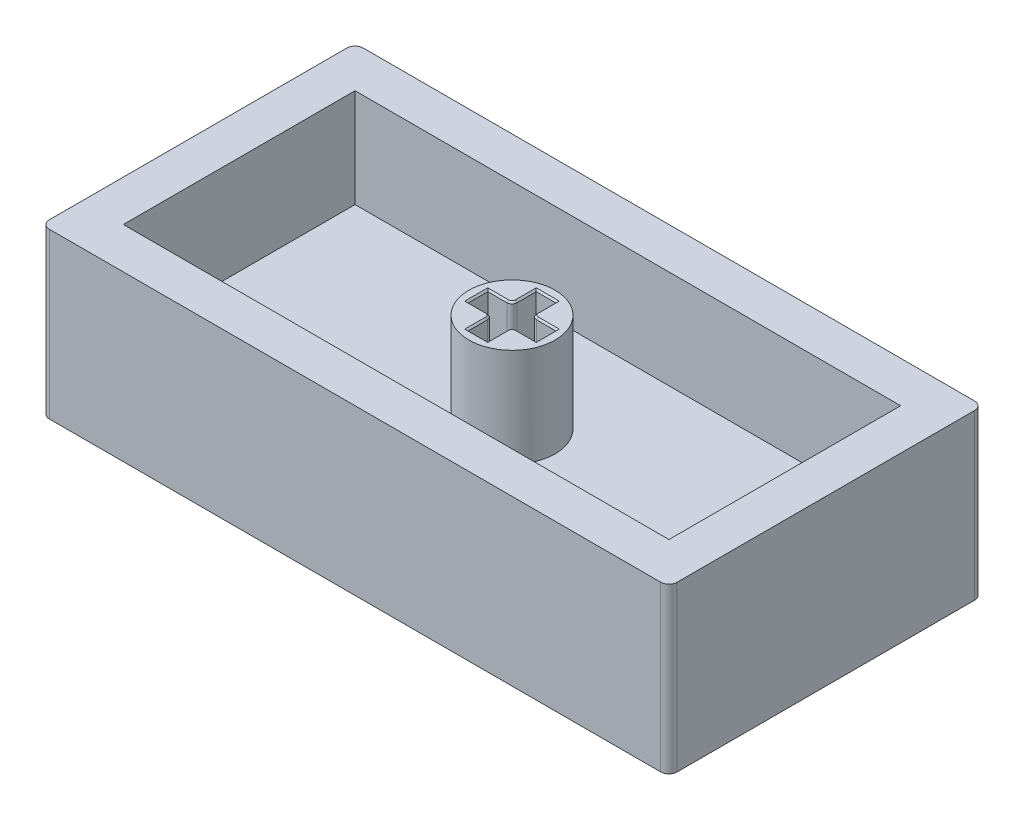
SolidWorks part; units mm, degrees
ref_plane "Front Plane" through (0, 0, 0) normal (0, 0, 1) x (1, 0, 0)
ref_plane "Top Plane" through (0, 0, 0) normal (0, 1, 0) x (1, 0, 0)
ref_plane "Right Plane" through (0, 0, 0) normal (1, 0, 0) x (0, 0, -1)
sketch "Sketch1" plane through (0, 0, 0) normal (0, 1, 0) x (1, 0, 0)
  line L0 (-16.6, -7.05) -> (-16.6, 7.05)
  line L1 (-7.05, -7.05) -> (7.05, -7.05) construction
  line L2 (-7.05, -7.05) -> (-7.05, 7.05) construction
  line L3 (-7.05, 7.05) -> (7.05, 7.05) construction
  line L4 (7.05, -7.05) -> (7.05, 7.05) construction
  line L5 (-7.05, -7.05) -> (7.05, 7.05) construction
  line L6 (-7.05, 7.05) -> (7.05, -7.05) construction
  line L7 (-19.1, -9.55) -> (19.1, -9.55)
  line L8 (-19.1, -9.55) -> (-19.1, 9.55)
  line L9 (-19.1, 9.55) -> (19.1, 9.55)
  line L10 (19.1, -9.55) -> (19.1, 9.55)
  line L11 (-19.1, -9.55) -> (19.1, 9.55) construction
  line L12 (-19.1, 9.55) -> (19.1, -9.55) construction
  line L13 (-16.6, 7.05) -> (16.6, 7.05)
  line L14 (16.6, -7.05) -> (16.6, 7.05)
  line L15 (-16.6, -7.05) -> (16.6, -7.05)
  point P0 (0, 0)
  point P6 (0, 0)
  dimension "D1" = 14.1
  dimension "D2" = 2.5
  dimension "D3" = 19.1
  dimension "D4" = 38.2
  dimension "D5" = 2.5
extrude "Boss-Extrude1" add sketch "Sketch1" along normal blind 10
extrude "Boss-Extrude2" add sketch "Sketch1<2>" along normal blind 4 contours L0 L15 L14 L13 region at (0, 0, 0)
sketch "Sketch1<2>" plane through (0, 0, 0) normal (0, 1, 0) x (1, 0, 0) same geometry as "Sketch1"
sketch "Sketch2" plane through (0, 4, 0) normal (0, 1, 0) x (1, 0, 0)
  line L1 (-2.075, -0.6) -> (2.075, -0.6)
  line L2 (-2.075, -0.6) -> (-2.075, 0.6)
  line L3 (-2.075, 0.6) -> (2.075, 0.6)
  line L4 (2.075, -0.6) -> (2.075, 0.6)
  line L5 (-2.075, -0.6) -> (2.075, 0.6) construction
  line L6 (-2.075, 0.6) -> (2.075, -0.6) construction
  line L7 (-0.6, -2.075) -> (0.6, -2.075)
  line L8 (-0.6, -2.075) -> (-0.6, 2.075)
  line L9 (-0.6, 2.075) -> (0.6, 2.075)
  line L10 (0.6, -2.075) -> (0.6, 2.075)
  line L11 (-0.6, -2.075) -> (0.6, 2.075) construction
  line L12 (-0.6, 2.075) -> (0.6, -2.075) construction
  line L13 (-0.9, -0.9) -> (0.9, -0.9) construction
  line L14 (-0.9, -0.9) -> (-0.9, 0.9) construction
  line L15 (-0.9, 0.9) -> (0.9, 0.9) construction
  line L16 (0.9, -0.9) -> (0.9, 0.9) construction
  line L17 (-0.9, -0.9) -> (0.9, 0.9) construction
  line L18 (-0.9, 0.9) -> (0.9, -0.9) construction
  circle A0 centre (0, 0) radius 2.625
  arc A1 (-0.9, 0.6) -> (-0.6, 0.9) centre (-0.9, 0.9) ccw
  arc A2 (0.6, 0.9) -> (0.9, 0.6) centre (0.9, 0.9) ccw
  arc A3 (0.9, -0.6) -> (0.6, -0.9) centre (0.9, -0.9) ccw
  arc A4 (-0.6, -0.9) -> (-0.9, -0.6) centre (-0.9, -0.9) ccw
  dimension "D1" = 5.25
  dimension "D4" = 0.3
  dimension "D2" = 1.2
  dimension "D3" = 4.15
extrude "Boss-Extrude3" add sketch "Sketch2" along normal up to surface (6 mm away) contours A0 L8 A4 L1 L2 L3 A1 L9 L10 A2 L4 A3 L7 region at (-2.5508, 4, 0) up to face at (0, 10, 0)
chamfer "Chamfer1" distance 0.1 angle 45 16 edges at (-0.6, 10, 1.4875) (0, 10, 2.075) (0.6, 10, 1.4875) (0.6879, 10, 0.6879) (1.4875, 10, 0.6) (2.075, 10, 0) (1.4875, 10, -0.6) (0.6879, 10, -0.6879) (0.6, 10, -1.4875) (0, 10, -2.075) (-0.6, 10, -1.4875) (-0.6879, 10, -0.6879) (-1.4875, 10, -0.6) (-2.075, 10, 0) (-1.4875, 10, 0.6) (-0.6879, 10, 0.6879)
fillet "Fillet1" radius 0.5 4 edges at (-19.1, 5, -9.55) (19.1, 5, -9.55) (19.1, 5, 9.55) (-19.1, 5, 9.55)
equation "\"Outer Circle Dia\"= 5.25"
equation "\"Long X Length\"= 4.15"
equation "\"Short X Length\"= 1.2"
equation "\"Fillet Rad\"= 0.3"
equation "\"Keycap Height\"= 10"
equation "\"D1@Sketch2\"=\"Outer Circle Dia\""
equation "\"D2@Sketch2\"=\"Short X Length\""
equation "\"D3@Sketch2\"=\"Long X Length\""
equation "\"D4@Sketch2\"=\"Fillet Rad\""
equation "\"D1@Boss-Extrude1\"=\"Keycap Height\""
equation "\"Keyswitch Hole Length\"= 14.1"
equation "\"D1@Sketch1\"=\"Keyswitch Hole Length\""
equation "\"D4@Sketch1\"=2*\"D3@Sketch1\""
equation "\"D1@Chamfer1\"=\"X Chamfer\""
equation "\"X Chamfer\"= 0.1"
equation "\"Outer Fillet\"= 0.5"
equation "\"D1@Fillet1\"=\"Outer Fillet\""
